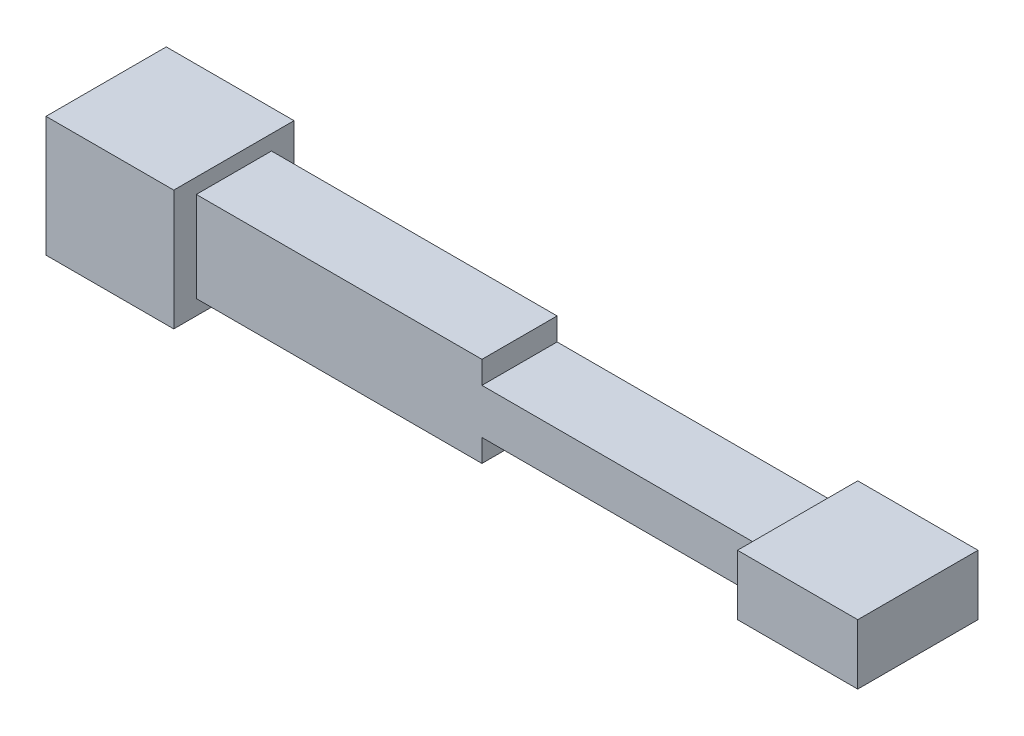
SolidWorks part; units mm, degrees
ref_plane "Front Plane" through (0, 0, 0) normal (0, 0, 1) x (1, 0, 0)
ref_plane "Top Plane" through (0, 0, 0) normal (0, 1, 0) x (1, 0, 0)
ref_plane "Right Plane" through (0, 0, 0) normal (1, 0, 0) x (0, 0, -1)
sketch "Sketch1" plane through (0, 0, 0) normal (0, 0, 1) x (1, 0, 0)
  line L0 (-54, 0) -> (54, 0) construction
  line L2 (54, -4) -> (38, -4)
  line L3 (54, -4) -> (54, 4)
  line L4 (54, 4) -> (38, 4)
  line L5 (38, -4) -> (38, 4)
  line L6 (54, -4) -> (38, 4) construction
  line L7 (54, 4) -> (38, -4) construction
  line L8 (-54, -8) -> (-37, -8)
  line L9 (-54, -8) -> (-54, 8)
  line L10 (-54, 8) -> (-37, 8)
  line L11 (-37, -8) -> (-37, 8)
  line L12 (-54, -8) -> (-37, 8) construction
  line L13 (-54, 8) -> (-37, -8) construction
  line L14 (-37, -6) -> (1, -6)
  line L15 (-37, -6) -> (-37, 6)
  line L16 (-37, 6) -> (1, 6)
  line L17 (1, -6) -> (1, 6)
  line L18 (-37, -6) -> (1, 6) construction
  line L19 (-37, 6) -> (1, -6) construction
  line L20 (1, -3) -> (38, -3)
  line L21 (1, -3) -> (1, 3)
  line L22 (1, 3) -> (38, 3)
  line L23 (38, -3) -> (38, 3)
  line L24 (1, -3) -> (38, 3) construction
  line L25 (1, 3) -> (38, -3) construction
  point P0 (46, 0)
  point P3 (54, 0)
  point P4 (0, 0)
  point P10 (-45.5, 0)
  point P15 (-54, 0)
  point P16 (-18, 0)
  point P21 (19.5, 0)
  dimension "D1" = 8
  dimension "D2" = 16
  dimension "D3" = 108
  dimension "D4" = 16
  dimension "D5" = 17
  dimension "D6" = 12
  dimension "D7" = 38
  dimension "D8" = 6
extrude "Boss-Extrude1" add sketch "Sketch1" along normal mid plane 16 contours L8 L11 L10 L9 | L5 L2 L3 L4 region at (46, 0, 0) region at (-45.5, 0, 0)
extrude "Boss-Extrude2" add sketch "Sketch1<3>" along normal mid plane 10 contours L14 L17 L16 L11 | L22 L17 L20 L5 region at (19.5, 0, 0) region at (-18, 0, 0)
sketch "Sketch1<3>" plane through (0, 0, 0) normal (0, 0, 1) x (1, 0, 0) same geometry as "Sketch1"
